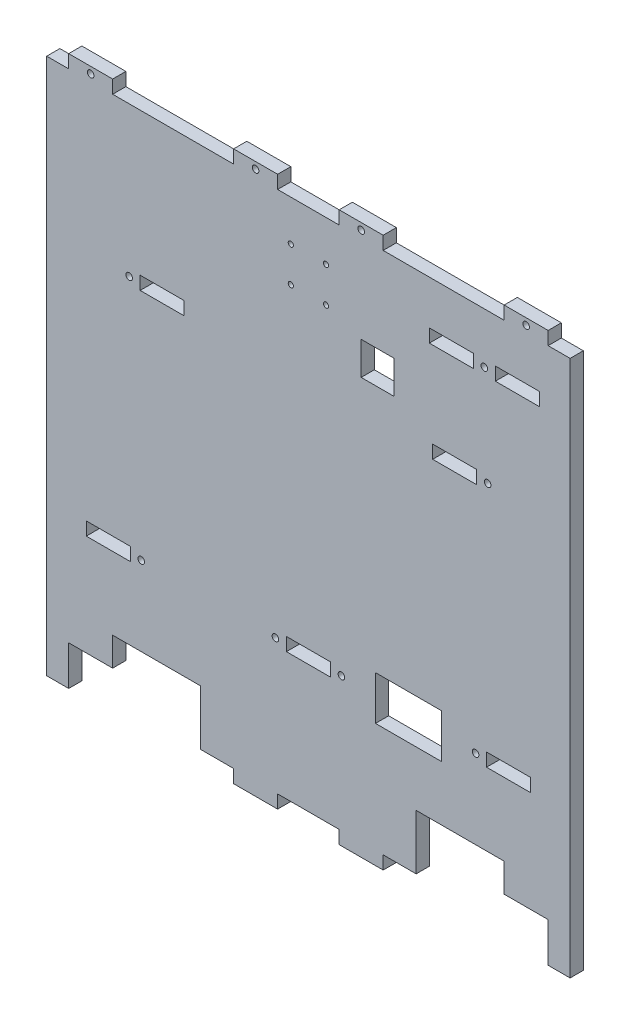
SolidWorks part; units mm, degrees
ref_plane "Plan de face" through (0, 0, 0) normal (0, 0, 1) x (1, 0, 0)
ref_plane "Plan de dessus" through (0, 0, 0) normal (0, 1, 0) x (1, 0, 0)
ref_plane "Plan de droite" through (0, 0, 0) normal (1, 0, 0) x (0, 0, -1)
sketch "Esquisse1" plane through (0, 0, 0) normal (0, 0, 1) x (1, 0, 0)
  line L0 (0, 139.6766) -> (0, -178.3461) construction
  line L1 (-109, 119) -> (109, 119)
  line L2 (-109, 119) -> (-109, -119)
  line L3 (-109, -119) -> (109, -119)
  line L4 (109, 119) -> (109, -119)
  line L5 (-101, -61) -> (-81, -61)
  line L6 (-101, -61) -> (-101, -55)
  line L7 (-101, -55) -> (-81, -55)
  line L8 (-81, -61) -> (-81, -55)
  line L9 (-10, -61) -> (10, -61)
  line L10 (-10, -61) -> (-10, -55)
  line L11 (-10, -55) -> (10, -55)
  line L12 (10, -61) -> (10, -55)
  line L13 (81, -61) -> (101, -61)
  line L14 (81, -61) -> (81, -55)
  line L15 (81, -55) -> (101, -55)
  line L16 (101, -61) -> (101, -55)
  line L17 (-76.5, 54) -> (-56.5, 54)
  line L18 (-76.5, 54) -> (-76.5, 48)
  line L19 (-76.5, 48) -> (-56.5, 48)
  line L20 (-56.5, 54) -> (-56.5, 48)
  line L21 (56.5, 54) -> (76.5, 54)
  line L22 (56.5, 54) -> (56.5, 48)
  line L23 (56.5, 48) -> (76.5, 48)
  line L24 (76.5, 54) -> (76.5, 48)
  line L25 (30.5, -69) -> (60.5, -69)
  line L26 (30.5, -69) -> (30.5, -49)
  line L27 (30.5, -49) -> (60.5, -49)
  line L28 (60.5, -69) -> (60.5, -49)
  line L30 (55, 99) -> (75, 99)
  line L31 (55, 99) -> (55, 93)
  line L32 (55, 93) -> (75, 93)
  line L33 (75, 99) -> (75, 93)
  line L34 (85, 99) -> (105, 99)
  line L35 (85, 99) -> (85, 93)
  line L36 (85, 93) -> (105, 93)
  line L37 (105, 99) -> (105, 93)
  line L38 (24, 64) -> (39, 64)
  line L39 (24, 64) -> (24, 79)
  line L40 (24, 79) -> (39, 79)
  line L41 (39, 64) -> (39, 79)
  dimension "D1" = 238
  dimension "D2" = 218
  dimension "D3" = 109
  dimension "D4" = 119
  dimension "D5" = 20
  dimension "D6" = 6
  dimension "D7" = 6
  dimension "D8" = 20
  dimension "D9" = 20
  dimension "D10" = 6
  dimension "D11" = 58
  dimension "D12" = 8
  dimension "D13" = 8
  dimension "D14" = 99
  dimension "D15" = 58
  dimension "D16" = 58
  dimension "D17" = 20
  dimension "D18" = 6
  dimension "D19" = 6
  dimension "D20" = 20
  dimension "D21" = 167
  dimension "D22" = 167
  dimension "D23" = 32.5
  dimension "D24" = 32.5
  dimension "D25" = 20
  dimension "D26" = 30
  dimension "D27" = 50
  dimension "D28" = 20.5
  dimension "D29" = 6
  dimension "D30" = 6
  dimension "D31" = 20
  dimension "D32" = 20
  dimension "D33" = 20
  dimension "D34" = 20
  dimension "D35" = 10
  dimension "D36" = 4
  dimension "D37" = 15
  dimension "D38" = 15
  dimension "D39" = 70
  dimension "D40" = 40
extrude "Boss.-Extru.1" add sketch "Esquisse1" along normal blind 6
sketch "Esquisse2" plane through (0, 0, 6) normal (0, 0, 1) x (1, 0, 0)
  line L0 (-109, -119) -> (109, -119) construction
  line L1 (-89, -119) -> (-49, -119)
  line L2 (-89, -119) -> (-89, -94)
  line L3 (-89, -94) -> (-49, -94)
  line L4 (-49, -119) -> (-49, -94)
  line L5 (-109, 119) -> (-109, -119) construction
  line L6 (49, -119) -> (89, -119)
  line L7 (49, -119) -> (49, -94)
  line L8 (49, -94) -> (89, -94)
  line L9 (89, -119) -> (89, -94)
  line L10 (109, -119) -> (109, 119) construction
  dimension "D1" = 40
  dimension "D2" = 20
  dimension "D3" = 40
  dimension "D4" = 20
  dimension "D5" = 25
  dimension "D6" = 25
extrude "Enlèv. mat.-Extru.1" cut sketch "Esquisse2" against normal blind 6
sketch "Esquisse3" plane through (0, 0, 6) normal (0, 0, 1) x (1, 0, 0)
  line L0 (0, 157.5653) -> (0, -190.6765) construction
  line L5 (-49, -119) -> (49, -119) construction
  line L6 (-34, -119) -> (-14, -119)
  line L7 (-34, -119) -> (-34, -125)
  line L8 (-34, -125) -> (-14, -125)
  line L9 (-14, -119) -> (-14, -125)
  line L10 (-49, -119) -> (-49, -94) construction
  line L15 (14, -119) -> (14, -125)
  line L16 (34, -125) -> (14, -125)
  line L17 (34, -119) -> (34, -125)
  line L18 (34, -119) -> (14, -119)
  line L19 (198.2674, 0) -> (-212.4835, 0) construction
  line L20 (0, -157.5653) -> (0, 190.6765) construction
  line L21 (34, 125) -> (14, 125)
  line L22 (14, 119) -> (14, 125)
  line L23 (89, 125) -> (109, 125)
  line L24 (89, 125) -> (89, 119)
  line L25 (89, 119) -> (109, 119)
  line L26 (109, 125) -> (109, 119)
  line L27 (-14, 119) -> (-14, 125)
  line L28 (-34, 125) -> (-14, 125)
  line L29 (-34, 119) -> (-34, 125)
  line L30 (-34, 119) -> (-14, 119)
  line L31 (-109, 125) -> (-109, 119)
  line L32 (-89, 119) -> (-109, 119)
  line L33 (-89, 125) -> (-89, 119)
  line L34 (-89, 125) -> (-109, 125)
  line L35 (34, 119) -> (14, 119)
  line L36 (34, 119) -> (34, 125)
  dimension "D2" = 20
  dimension "D3" = 6
  dimension "D4" = 15
extrude "Boss.-Extru.3" add sketch "Esquisse3" against normal blind 6
sketch "Esquisse4" plane through (0, 0, 6) normal (0, 0, 1) x (1, 0, 0)
  line L0 (-111.0944, 51) -> (126.4062, 51) construction
  line L1 (116.6655, -58) -> (-122.9189, -58) construction
  line L2 (76.5, 48) -> (76.5, 54) construction
  line L3 (0, 153.5677) -> (0, -173.1111) construction
  line L4 (45.0686, 96) -> (109.1297, 96) construction
  line L5 (81, -55) -> (81, -61) construction
  line L6 (10, -61) -> (10, -55) construction
  line L7 (-10, -55) -> (-10, -61) construction
  line L8 (75, 93) -> (75, 99) construction
  line L9 (-114.2336, 122) -> (-6.2018, 122) construction
  line L10 (-56.5, 54) -> (-76.5, 54) construction
  line L11 (-89, 125) -> (-109, 125) construction
  line L12 (-34, 125) -> (-34, 119) construction
  line L13 (55, 93) -> (75, 93) construction
  line L14 (-89, 119) -> (-89, 125) construction
  circle A0 centre (-15, -58) radius 1.5
  circle A1 centre (-76, -58) radius 1.5
  circle A2 centre (80, 96) radius 1.5
  circle A3 centre (81.5, 51) radius 1.5
  circle A4 centre (76, -58) radius 1.5
  circle A5 centre (15, -58) radius 1.5
  circle A6 centre (-81.5, 51) radius 1.5
  circle A7 centre (-99, 122) radius 1.5
  circle A8 centre (-24, 122) radius 1.5
  circle A9 centre (24, 122) radius 1.5
  circle A10 centre (99, 122) radius 1.5
  dimension "D2" = 5
  dimension "D3" = 3
  dimension "D4" = 3
  dimension "D5" = 5
  dimension "D6" = 5
  dimension "D7" = 3
  dimension "D8" = 3
  dimension "D9" = 3
  dimension "D10" = 5
  dimension "D11" = 3
  dimension "D12" = 5
  dimension "D13" = 3
  dimension "D15" = 3
  dimension "D16" = 3
  dimension "D17" = 10
  dimension "D18" = 10
  dimension "D14" = 3
extrude "Enlèv. mat.-Extru.2" cut sketch "Esquisse4" against normal blind 6
sketch "Esquisse5" plane through (0, 0, 6) normal (0, 0, 1) x (1, 0, 0)
  line L0 (-109, 119) -> (-109, -125)
  line L1 (-109, 119) -> (-119, 119)
  line L2 (-109, -125) -> (-119, -125)
  line L3 (-119, 119) -> (-119, -125)
  line L5 (109, -125) -> (109, 119)
  line L6 (109, -125) -> (119, -125)
  line L7 (109, 119) -> (119, 119)
  line L8 (119, -125) -> (119, 119)
  line L11 (109, 125) -> (89, 125) construction
  line L12 (-89, 125) -> (-109, 125) construction
  dimension "D1" = 10
  dimension "D2" = 10
  dimension "D3" = 244
  dimension "D4" = 244
  dimension "D5" = 6
  dimension "D6" = 6
extrude "Boss.-Extru.4" add sketch "Esquisse5" against normal blind 6
sketch "Esquisse6" plane through (0, 0, 6) normal (0, 0, 1) x (1, 0, 0)
  line L0 (0, 108.4917) -> (0, -172.5759) construction
  line L1 (89, -119) -> (109, -119)
  line L2 (89, -119) -> (89, -107)
  line L3 (89, -107) -> (109, -107)
  line L4 (109, -119) -> (109, -107)
  line L5 (-109, -119) -> (-109, -107)
  line L6 (-89, -107) -> (-109, -107)
  line L7 (-89, -119) -> (-89, -107)
  line L8 (-89, -119) -> (-109, -119)
  dimension "D1" = 12
  dimension "D2" = 20
extrude "Enlèv. mat.-Extru.3" cut sketch "Esquisse6" against normal blind 6
sketch "Esquisse7" plane through (0, 0, 6) normal (0, 0, 1) x (1, 0, 0)
  line L0 (14, 119) -> (-14, 119) construction
  line L1 (14, 125) -> (14, 119) construction
  circle A0 centre (-8, 100.5) radius 1.175
  circle A1 centre (8, 100.5) radius 1.175
  circle A2 centre (-8, 84.5) radius 1.175
  circle A3 centre (8, 84.5) radius 1.175
  dimension "D1" = 16
  dimension "D7" = 2.35
  dimension "D8" = 2.35
  dimension "D9" = 2.35
  dimension "D10" = 2.35
  dimension "D2" = 16
  dimension "D3" = 16
  dimension "D4" = 16
  dimension "D5" = 18.5
  dimension "D6" = 6
  dimension "D11" = 18.5
extrude "Enlèv. mat.-Extru.4" cut sketch "Esquisse7" against normal through all
equation "\"D3@Esquisse1\"=\"D2@Esquisse1\"/2"
equation "\"D4@Esquisse1\"=\"D1@Esquisse1\"/2"
